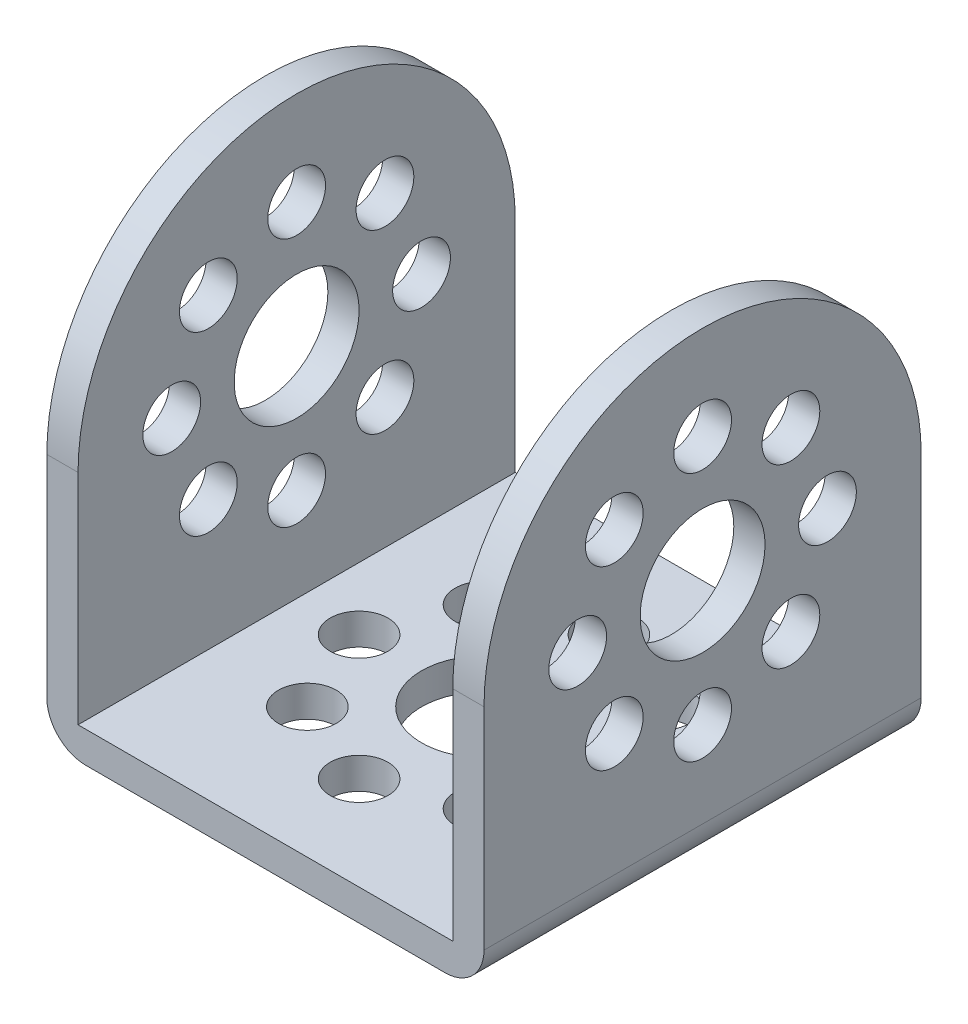
SolidWorks part; units mm, degrees
material "2024 Alloy"
ref_plane "Front Plane" through (0, 0, 0) normal (0, 0, 1) x (1, 0, 0)
ref_plane "Top Plane" through (0, 0, 0) normal (0, 1, 0) x (1, 0, 0)
ref_plane "Right Plane" through (0, 0, 0) normal (1, 0, 0) x (0, 0, -1)
sketch "Sketch1" plane through (0, 0, 0) normal (1, 0, 0) x (0, 0, -1)
  line L0 (-14, 0) -> (-14, -16)
  line L1 (-14, -16) -> (14, -16)
  line L2 (14, -16) -> (14, 0)
  line L3 (0, 0) -> (0, -16) construction
  line L4 (0, 0) -> (0, 8) construction
  arc A0 (14, 0) -> (-14, 0) centre (0, 0) ccw
  circle A1 centre (0, 0) radius 4
  circle A2 centre (0, 8) radius 1.85
  circle A3 centre (5.6569, 5.6569) radius 1.85
  circle A4 centre (8, 0) radius 1.85
  circle A5 centre (5.6569, -5.6569) radius 1.85
  circle A6 centre (0, -8) radius 1.85
  circle A7 centre (-5.6569, -5.6569) radius 1.85
  circle A8 centre (-8, 0) radius 1.85
  circle A9 centre (-5.6569, 5.6569) radius 1.85
  point P7 (0, -16)
  point P27 (0, 0)
  dimension "D3" = 14
  dimension "D4" = 8
  dimension "D6" = 3.7
  dimension "D1" = 16
  dimension "D2" = 28
  dimension "D5" = 8
  dimension "D7" = 8
extrude "Boss-Extrude1" add sketch "Sketch1" along normal blind 14 and the other way blind 14
sketch "Sketch2" plane through (0, 0, 0) normal (1, 0, 0) x (0, 0, -1)
  line L0 (-14, 0) -> (-14, -14)
  line L1 (-14, -14) -> (14, -14)
  line L2 (14, -14) -> (14, 0)
  arc A1 (14, 0) -> (-14, 0) centre (0, 0) ccw
  dimension "D1" = 14
  dimension "D2" = 14
extrude "Cut-Extrude1" cut sketch "Sketch2" against normal blind 12 and the other way blind 12
sketch "Sketch3" plane through (0, -16, 0) normal (0, -1, 0) x (1, 0, 0)
  line L0 (0, 14) -> (0, -14) construction
  line L1 (-14, 14) -> (14, 14) construction
  line L2 (-14, -14) -> (14, -14) construction
  line L3 (14, 0) -> (-14, 0) construction
  line L4 (14, 14) -> (14, -14) construction
  line L5 (-14, 14) -> (-14, -14) construction
  circle A0 centre (0, 0) radius 4
  circle A1 centre (0, 8) radius 1.85
  circle A2 centre (5.6569, 5.6569) radius 1.85
  circle A3 centre (8, 0) radius 1.85
  circle A4 centre (5.6569, -5.6569) radius 1.85
  circle A5 centre (0, -8) radius 1.85
  circle A6 centre (-5.6569, -5.6569) radius 1.85
  circle A7 centre (-8, 0) radius 1.85
  circle A8 centre (-5.6569, 5.6569) radius 1.85
  point P32 (0, 0)
  dimension "D1" = 8
  dimension "D3" = 3.7
  dimension "D2" = 8
  dimension "D4" = 8
extrude "Cut-Extrude2" cut sketch "Sketch3" against normal blind 2
fillet "Fillet1" radius 2.5 2 edges at (-14, -16, 0) (14, -16, 0)
